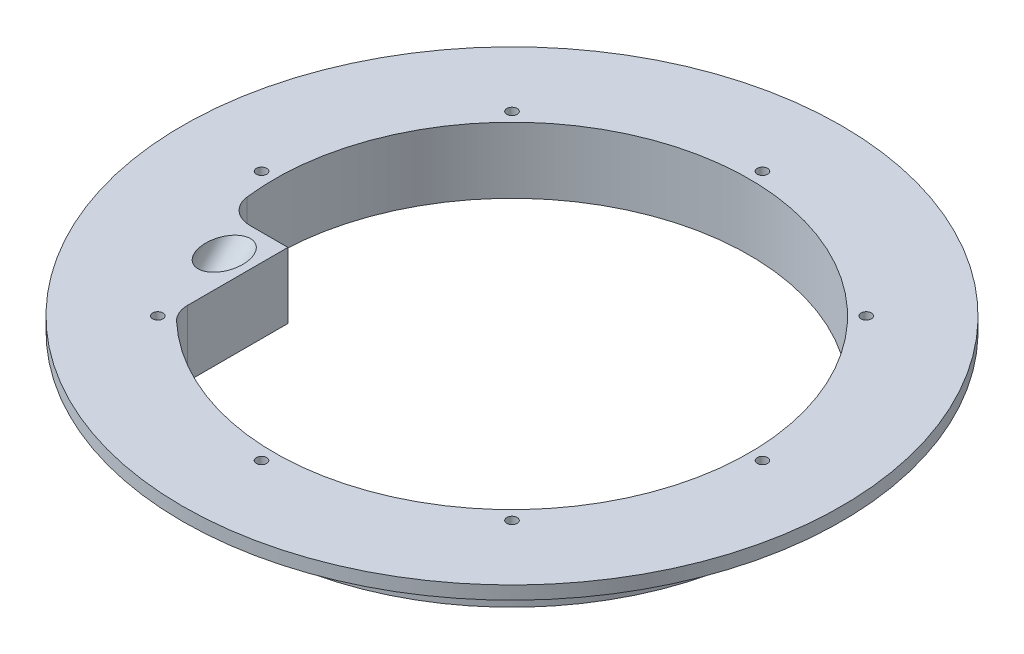
SolidWorks part; units mm, degrees
material "AISI 316 Annealed Stainless Steel Bar (SS)"
ref_plane "Front Plane" through (0, 0, 0) normal (0, 0, 1) x (1, 0, 0)
ref_plane "Top Plane" through (0, 0, 0) normal (0, 1, 0) x (1, 0, 0)
ref_plane "Right Plane" through (0, 0, 0) normal (1, 0, 0) x (0, 0, -1)
sketch "Sketch7" plane through (0, 0, 0) normal (0, 1, 0) x (1, 0, 0)
  line L0 (-111.442, -25.4) -> (-82.55, -25.4)
  line L1 (-82.55, -25.4) -> (-82.55, -79.0569)
  circle A0 centre (0, 0) radius 158.75
  circle A1 centre (0, 0) radius 114.3
  circle A2 centre (0, 0) radius 127
  circle A3 centre (0, 0) radius 152.4
  arc A4 (-82.55, -73.7803) -> (-78.5812, -83.0029) centre (-69.85, -73.7803) ccw
  arc A5 (-113.4035, -14.2875) -> (-100.8031, -25.4) centre (-100.8031, -12.7) ccw
  point P12 (0, 0)
  point P13 (0, 0)
  dimension "D1" = 317.5
  dimension "D2" = 6.35
  dimension "D5" = 12.7
  dimension "D6" = 25.4
  dimension "D7" = 12.7
  dimension "D8" = 12.7
  dimension "D3" = 25.4
  dimension "D4" = 82.55
extrude "Boss-Extrude2" add sketch "Sketch7" against normal blind 6.35 contours A0 A3 | A3 A2 region at (-154.2599, 0, 0) region at (-148.0895, 0, 0)
extrude "Boss-Extrude3" add sketch "Sketch7<3>" against normal blind 31.75 contours A2 A1 | L0 A1 L1 | A5 A1 L0 | A4 L1 A1 region at (-109.6479, 0, 22.9902) region at (-93.302, 0, 45.0242) region at (-81.7447, 0, 78.8103) region at (-123.4079, 0, 0)
sketch "Sketch7<3>" plane through (0, 0, 0) normal (0, 1, 0) x (1, 0, 0) same geometry as "Sketch7"
ref_plane "Plane1" through (0, -12.7, 12.7) normal (0, 0.7071, -0.7071) x (1, 0, 0)
hole_wizard "Pipe Tap Drill for 1/2 Tap2" positions "Sketch10" profile "Sketch12" hole size "1/2" standard "ANSI Inch"
sketch "Sketch10" plane through (0, -12.7, 12.7) normal (0, 0.7071, -0.7071) x (1, 0, 0)
  line L0 (-82.55, -17.9605) -> (-95.25, -17.9605) construction
  line L1 (-100.8031, -17.9605) -> (-82.55, -17.9605) construction
  line L2 (-95.25, -17.9605) -> (-95.25, -30.6605) construction
  point P0 (-95.25, -30.6605)
  dimension "D1" = 12.7
  dimension "D2" = 12.7
sketch "Sketch12" plane through (-95.25, 8.9803, 34.3803) normal (1, 0, 0) x (0, 0.7071, 0.7071)
  line L0 (0, 0) -> (0, 37.1145)
  line L1 (0, 37.1145) -> (8.9281, 31.75)
  line L2 (8.9281, 31.75) -> (8.9281, 0)
  line L5 (8.9281, 0) -> (0, 0)
  line L10 (0, 37.1145) -> (-8.9281, 31.75) construction
  line L11 (0, -6.35) -> (0, 107.95) construction
  dimension "Hole Dia." = 17.8562
  dimension "Hole Depth" = 31.75
  dimension "Drill Angle" = 118
ref_plane "Plane2" through (0, 0, 127) normal (0, 0, 1) x (1, 0, 0)
hole_wizard "1/2 (0.5) Diameter Hole3" positions "Sketch13" profile "Sketch14" hole size "1/2" standard "ANSI Inch"
sketch "Sketch13" plane through (0, 0, 127) normal (0, 0, 1) x (1, 0, 0)
  line L0 (-82.55, 0) -> (-95.25, 0) construction
  line L2 (-95.25, 0) -> (-95.25, -19.05) construction
  point P0 (-95.25, -19.05)
  dimension "D1" = 12.7
  dimension "D2" = 19.05
sketch "Sketch14" plane through (-95.25, -19.05, 127) normal (1, 0, 0) x (0, -1, 0)
  line L0 (0, 0) -> (0, 66.0455)
  line L1 (0, 66.0455) -> (6.35, 62.23)
  line L2 (6.35, 62.23) -> (6.35, 0)
  line L5 (6.35, 0) -> (0, 0)
  line L10 (0, 66.0455) -> (-6.35, 62.23) construction
  line L11 (0, -6.35) -> (0, 107.95) construction
  dimension "Hole Dia." = 12.7
  dimension "Hole Depth" = 62.23
  dimension "Drill Angle" = 118
hole_wizard "1/2 (0.5) Diameter Hole4" positions "Sketch18" profile "Sketch19" hole size "1/2" standard "ANSI Inch"
sketch "Sketch18" plane through (0, -12.7, 12.7) normal (0, 0.7071, -0.7071) x (1, 0, 0)
  point P0 (-95.25, -30.6605)
sketch "Sketch19" plane through (-95.25, 8.9803, 34.3803) normal (1, 0, 0) x (0, 0.7071, 0.7071)
  line L0 (0, 0) -> (0, 43.1855)
  line L1 (0, 43.1855) -> (6.35, 39.37)
  line L2 (6.35, 39.37) -> (6.35, 0)
  line L5 (6.35, 0) -> (0, 0)
  line L10 (0, 43.1855) -> (-6.35, 39.37) construction
  line L11 (0, -6.35) -> (0, 107.95) construction
  dimension "Hole Dia." = 12.7
  dimension "Hole Depth" = 39.37
  dimension "Drill Angle" = 118
hole_wizard "#10 Clearance Hole1" positions "Sketch20" profile "Sketch21" hole size "#10" standard "ANSI Inch" end condition through all
sketch "Sketch20" plane through (0, 0, 0) normal (0, 1, 0) x (1, 0, 0)
  line L0 (0, -114.3) -> (0, -120.65) construction
  arc A0 (-78.5812, -83.0029) -> (-113.4035, -14.2875) centre (0, 0) ccw construction
  point P0 (0, -120.65)
  point P10 (-3.4054, -117.4243)
  dimension "D1" = 6.35
sketch "Sketch21" plane through (0, 0, 120.65) normal (1, 0, 0) x (0, 0, 1)
  line L0 (0, 0) -> (0, 31.75)
  line L1 (0, 31.75) -> (2.4892, 31.75)
  line L2 (2.4892, 31.75) -> (2.4892, 0)
  line L5 (2.4892, 0) -> (0, 0)
  line L11 (0, -6.35) -> (0, 107.95) construction
  dimension "Thru Hole Dia." = 4.9784
  dimension "Thru Hole Depth" = 31.75
pattern_circular "CirPattern1" count 8 over 360 about axis through (0, -31.75, 0) along (0, 1, 0) of "#10 Clearance Hole1"
